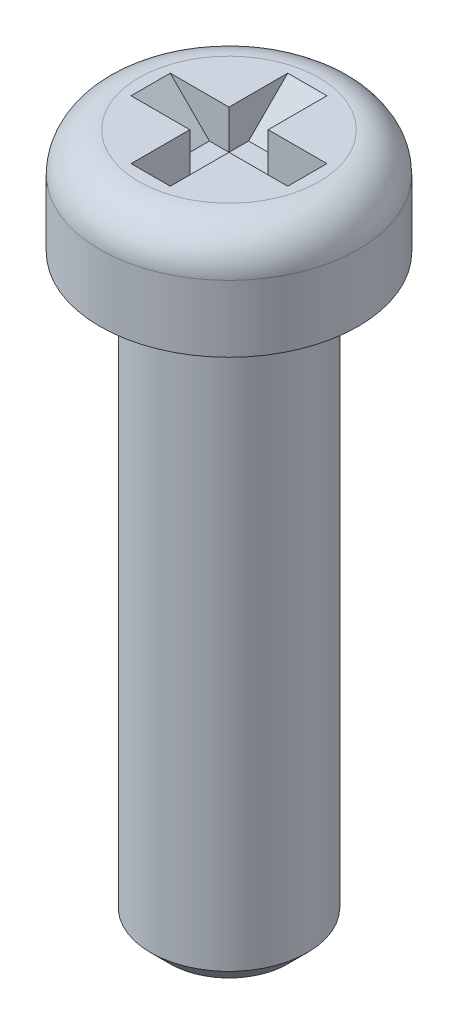
SolidWorks part; units mm, degrees
ref_plane "前视基准面" through (0, 0, 0) normal (0, 0, 1) x (1, 0, 0)
ref_plane "上视基准面" through (0, 0, 0) normal (0, 1, 0) x (1, 0, 0)
ref_plane "右视基准面" through (0, 0, 0) normal (1, 0, 0) x (0, 0, -1)
other "Configuration Table"
sketch "草图1" plane through (0, 0, 0) normal (0, 1, 0) x (1, 0, 0)
  circle A0 centre (0, 0) radius 2
  dimension "D1" = 4
extrude "凸台-拉伸1" add sketch "草图1" along normal blind 15
cosmetic thread "装饰螺纹线1" parameters "D2"=3
sketch "草图2" plane through (0, 15, 0) normal (0, 1, 0) x (1, 0, 0)
  circle A0 centre (0, 0) radius 3.3
  dimension "D1" = 6.6
extrude "凸台-拉伸2" add sketch "草图2" along normal blind 2.7
fillet "圆角1" radius 1 1 edges at (0, 17.7, 3.3)
chamfer "倒角1" distance 0.5 angle 45 1 edges at (0, 0, 2)
sketch "草图3" plane through (0, 17.7, 0) normal (0, 1, 0) x (1, 0, 0)
  line L0 (-2, 0) -> (2, 0)
  line L1 (0, 2) -> (0, -2)
  point P5 (0, 0)
  point P9 (0, 0)
  dimension "D1" = 4
  dimension "D2" = 4
extrude "切除-拉伸-薄壁1" cut sketch "草图3" against normal blind 1 thin thin type mid plane wall 1
chamfer "倒角2" distance 1 angle 45 4 edges at (0, 16.7, 2) (2, 16.7, 0) (0, 16.7, -2) (-2, 16.7, 0)
